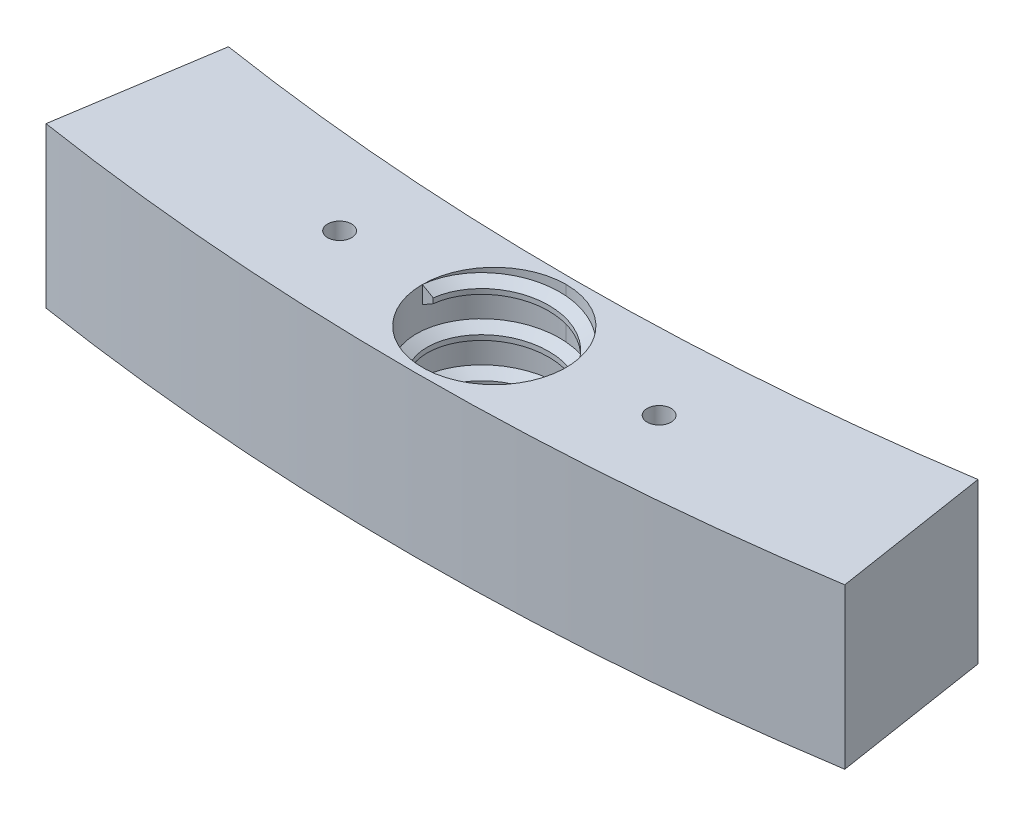
SolidWorks part; units mm, degrees
ref_plane "Front Plane" through (0, 0, 0) normal (0, 0, 1) x (1, 0, 0)
ref_plane "Top Plane" through (0, 0, 0) normal (0, 1, 0) x (1, 0, 0)
ref_plane "Right Plane" through (0, 0, 0) normal (1, 0, 0) x (0, 0, -1)
sketch "Sketch1" plane through (0, 0, 0) normal (0, 1, 0) x (1, 0, 0)
  line L0 (-50, -304.5) -> (50, -304.5) construction
  line L1 (-50, -304.5) -> (-50, -320.6248) construction
  line L2 (50, -304.5) -> (50, -320.6248) construction
  line L3 (-50, -320.6248) -> (-46.9183, -300.8636)
  line L4 (50, -320.6248) -> (46.9183, -300.8636)
  arc A0 (-314.5, 0) -> (314.5, 0) centre (0, 0) ccw
  arc A1 (-324.5, 0) -> (324.5, 0) centre (0, 0) ccw
  arc A2 (-304.5, 0) -> (304.5, 0) centre (0, 0) ccw
  circle A3 centre (0, -314.5) radius 9
  circle A4 centre (20, -313.8634) radius 1.5
  circle A5 centre (-20, -313.8634) radius 1.5
  point P13 (0, -304.5)
  dimension "D1" = 10
  dimension "D4" = 18
  dimension "D6" = 3
  dimension "D8" = 3
  dimension "D3" = 100
  dimension "D5" = 20
  dimension "D7" = 20
  dimension "D2" = 10
extrude "Boss-Extrude1" add sketch "Sketch1" along normal blind 20 contours L3 A1 L4 A0 | A2 L3 A0 L4
sketch "Sketch3" plane through (0, 0, 0) normal (0, -1, 0) x (-1, 0, 0)
  circle A0 centre (0, -314.5) radius 9
extrude "Boss-Extrude2" add sketch "Sketch3" against normal blind 2
thread "Thread1" pitch 2.5 start angle 0, offset 0, length 0, pitch 5, diameter 18
ref_plane "Plane1" through (-9, 20, 314.5) normal (0, 0, 1) x (-1, 0, 0)
sketch "Thread Profile1" plane through (-9, 20, 314.5) normal (0, 0, 1) x (-1, 0, 0)
  line L0 (0, 0) -> (0, 2.5) construction
  line L11 (0, 0) -> (0, 2.1875)
  line L12 (0, 2.1875) -> (-1.3532, 1.4062)
  line L13 (-1.3532, 1.4062) -> (-1.3532, 0.7812)
  line L15 (-1.3532, 0.7812) -> (0, 0)
  line L17 (-1.3532, 1.0937) -> (0, 1.0937) construction
  point P2 (0, 0)
  dimension "Pitch" = 2.5
  dimension "Profile_Angle" = 60
  dimension "Profile_Land" = 0.625
  dimension "Profile_Height" = 1.3532
